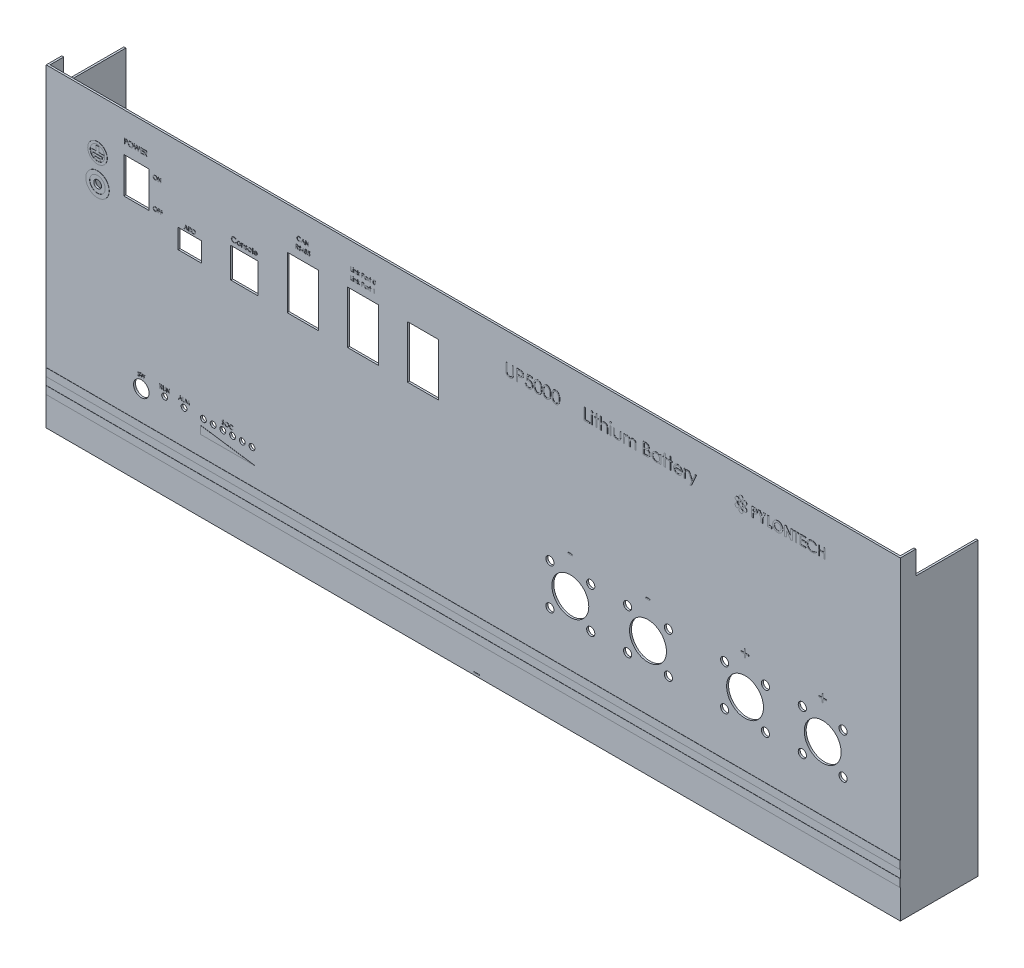
SolidWorks part; units mm, degrees
ref_plane "Front Plane" through (0, 0, 0) normal (0, 0, 1) x (1, 0, 0)
ref_plane "Top Plane" through (0, 0, 0) normal (0, 1, 0) x (1, 0, 0)
ref_plane "Right Plane" through (0, 0, 0) normal (1, 0, 0) x (0, 0, -1)
sketch "Sketch1" plane through (0, 0, 0) normal (0, 1, 0) x (1, 0, 0)
  line L0 (-220, 40) -> (-219, 40)
  line L1 (-220, 0) -> (220, 0)
  line L2 (0, 0) -> (0, 1) construction
  line L3 (-219, 1) -> (219, 1)
  line L6 (220, 0) -> (220, 40)
  line L7 (220, 40) -> (219, 40)
  line L8 (219, 1) -> (219, 40)
  line L9 (-219, 1) -> (-219, 40)
  line L10 (-220, 0) -> (-220, 40)
  dimension "D1" = 1
  dimension "D2" = 40
  dimension "D3" = 1
  dimension "D4" = 440
extrude "Boss-Extrude1" add sketch "Sketch1" along normal blind 162
sketch "Sketch2" plane through (220, 0, 0) normal (1, 0, 0) x (0, 0, -1)
  line L0 (0, 162) -> (0, 0) construction
  line L1 (40, 162) -> (8, 162)
  line L2 (40, 162) -> (40, 150)
  line L3 (40, 150) -> (8, 150)
  line L4 (8, 162) -> (8, 150)
  dimension "D1" = 8
  dimension "D2" = 12
extrude "Cut-Extrude1" cut sketch "Sketch2" against normal through all
sketch "Sketch3" plane through (0, 0, 0) normal (0, 0, 1) x (1, 0, 0)
  line L0 (50, 60) -> (90, 60) construction
  line L1 (-180, 142) -> (-167, 142)
  line L2 (-180, 142) -> (-180, 123.5)
  line L3 (-180, 123.5) -> (-167, 123.5)
  line L4 (-167, 142) -> (-167, 123.5)
  line L5 (-152, 123.5) -> (-140, 123.5)
  line L6 (-152, 123.5) -> (-152, 113.5)
  line L7 (-152, 113.5) -> (-140, 113.5)
  line L8 (-140, 123.5) -> (-140, 113.5)
  line L9 (-125, 129) -> (-110.8, 129)
  line L10 (-125, 129) -> (-125, 113.5)
  line L11 (-125, 113.5) -> (-110.8, 113.5)
  line L12 (-110.8, 129) -> (-110.8, 113.5)
  line L13 (-95.8, 140.5) -> (-79.8, 140.5)
  line L14 (-95.8, 140.5) -> (-95.8, 113.5)
  line L15 (-95.8, 113.5) -> (-79.8, 113.5)
  line L16 (-79.8, 140.5) -> (-79.8, 113.5)
  line L17 (-64.8, 140.5) -> (-48.8, 140.5)
  line L18 (-64.8, 140.5) -> (-64.8, 113.5)
  line L19 (-64.8, 113.5) -> (-48.8, 113.5)
  line L20 (-48.8, 140.5) -> (-48.8, 113.5)
  line L21 (90, 60) -> (70, 60) construction
  line L22 (70, 60) -> (70, 70.5) construction
  line L23 (70, 70.5) -> (60.5, 70.5) construction
  line L24 (140, 60) -> (180, 60) construction
  line L25 (180, 60) -> (160, 60) construction
  line L26 (160, 60) -> (160, 70.5) construction
  line L27 (160, 70.5) -> (150.5, 70.5) construction
  line L28 (-220, 0) -> (220, 0) construction
  line L29 (220, 162) -> (220, 0) construction
  line L30 (-220, 162) -> (220, 162) construction
  line L31 (-220, 162) -> (-220, 0) construction
  line L32 (-193.5, 122) -> (-173.5, 122) construction
  line L33 (-173.5, 122) -> (-173.5, 142) construction
  line L34 (-140, 113.5) -> (-125, 113.5) construction
  line L35 (-110.8, 113.5) -> (-95.8, 113.5) construction
  line L36 (-79.8, 113.5) -> (-64.8, 113.5) construction
  line L37 (-48.8, 113.5) -> (-33.8, 113.5) construction
  line L39 (-33.8, 113.5) -> (-17.8, 113.5)
  line L40 (-33.8, 113.5) -> (-33.8, 140.5)
  line L41 (-33.8, 140.5) -> (-17.8, 140.5)
  line L42 (-17.8, 113.5) -> (-17.8, 140.5)
  circle A0 centre (-193.5, 122) radius 2
  circle A1 centre (50, 60) radius 9.5
  circle A5 centre (60.5, 70.5) radius 2.1
  circle A6 centre (60.5, 49.5) radius 2.1
  circle A7 centre (39.5, 49.5) radius 2.1
  circle A8 centre (39.5, 70.5) radius 2.1
  circle A9 centre (100.5, 70.5) radius 2.1
  circle A10 centre (100.5, 49.5) radius 2.1
  circle A11 centre (90, 60) radius 9.5
  circle A12 centre (79.5, 49.5) radius 2.1
  circle A13 centre (79.5, 70.5) radius 2.1
  circle A14 centre (140, 60) radius 9.5
  circle A15 centre (150.5, 70.5) radius 2.1
  circle A16 centre (150.5, 49.5) radius 2.1
  circle A17 centre (129.5, 49.5) radius 2.1
  circle A18 centre (129.5, 70.5) radius 2.1
  circle A19 centre (190.5, 70.5) radius 2.1
  circle A20 centre (190.5, 49.5) radius 2.1
  circle A21 centre (180, 60) radius 9.5
  circle A22 centre (169.5, 49.5) radius 2.1
  circle A23 centre (169.5, 70.5) radius 2.1
  point P35 (50, 60)
  point P59 (140, 60)
  dimension "D3" = 19
  dimension "D5" = 4.2
  dimension "D14" = 4
  dimension "D2" = 21
  dimension "D6" = 40
  dimension "D7" = 60
  dimension "D8" = 50
  dimension "D9" = 40
  dimension "D10" = 13
  dimension "D11" = 18.5
  dimension "D12" = 20
  dimension "D13" = 40
  dimension "D15" = 20
  dimension "D16" = 20
  dimension "D17" = 12
  dimension "D18" = 10
  dimension "D19" = 15
  dimension "D20" = 15
  dimension "D21" = 15.5
  dimension "D22" = 14.2
  dimension "D23" = 16
  dimension "D24" = 27
  dimension "D4" = 2
  dimension "D1" = 4
extrude "Cut-Extrude2" cut sketch "Sketch3" against normal blind 132
sketch "Sketch4" plane through (0, 0, 0) normal (0, 0, 1) x (1, 0, 0)
  line L0 (-220, 162) -> (-220, 0) construction
  line L1 (-220, 27) -> (220, 27)
  line L2 (-220, 27) -> (-220, 23)
  line L3 (-220, 23) -> (220, 23)
  line L4 (220, 27) -> (220, 23)
  line L5 (220, 162) -> (220, 0) construction
  line L6 (220, 81) -> (-220, 81) construction
  line L7 (-220, 19) -> (220, 19)
  line L8 (-220, 19) -> (-220, 15)
  line L9 (-220, 15) -> (220, 15)
  line L10 (220, 19) -> (220, 15)
  line L11 (0, 27) -> (0, 23) construction
  line L12 (0, 23) -> (0, 19) construction
  line L13 (0, 19) -> (0, 15) construction
  line L14 (0, 21) -> (220, 21) construction
  line L15 (0, 27) -> (0, 142) construction
  line L16 (0, 142) -> (220, 142) construction
  line L17 (-193.5, 122) -> (-193.5, 136) construction
  line L18 (-193.5, 136) -> (-192.75, 136) construction
  line L55 (-194.25, 132.6) -> (-192.75, 132.6) construction
  line L57 (-192.75, 136) -> (-190.25, 136) construction
  line L58 (-196.75, 136.5) -> (-192.75, 136.5) construction
  line L59 (-196.75, 136.5) -> (-196.75, 135.5) construction
  line L61 (-190.25, 136.5) -> (-190.25, 135.5) construction
  line L66 (-195, 132.9) -> (-194.25, 132.9) construction
  line L67 (-195, 132.9) -> (-195, 133.9) construction
  line L69 (-192, 132.9) -> (-192, 133.9) construction
  line L70 (-194.25, 135.2) -> (-195.9628, 135.2) construction
  line L73 (-192.75, 132.9) -> (-192, 132.9) construction
  line L74 (-194.25, 132.6) -> (-194.25, 132.9) construction
  line L75 (-195, 133.9) -> (-194.25, 133.9) construction
  line L80 (-194.25, 135.5) -> (-196.75, 135.5) construction
  line L81 (-196.75, 136.5) -> (-194.25, 136.5) construction
  line L83 (-192.75, 139.1) -> (-192.75, 136.5) construction
  line L84 (-192.75, 136.5) -> (-190.25, 136.5) construction
  line L85 (-190.25, 135.5) -> (-192.75, 135.5) construction
  line L86 (-192.75, 135.5) -> (-192.75, 135.2) construction
  line L87 (-192.75, 135.2) -> (-191.0372, 135.2) construction
  line L90 (-192.75, 133.9) -> (-192, 133.9) construction
  line L91 (-192.75, 132.6) -> (-192.75, 132.9) construction
  line L107 (-194.25, 136.5) -> (-196.75, 136.5) construction
  line L108 (-196.75, 136.5) -> (-196.75, 135.5) construction
  line L115 (-194.25, 133.9) -> (-195, 133.9) construction
  line L116 (-195, 133.9) -> (-195, 132.9) construction
  line L117 (-195, 132.9) -> (-194.25, 132.9) construction
  line L119 (-192.75, 139.1) -> (-192.75, 136.5) construction
  line L120 (-192.75, 136.5) -> (-190.25, 136.5) construction
  line L121 (-190.25, 136.5) -> (-190.25, 135.5) construction
  line L122 (-190.25, 135.5) -> (-192.75, 135.5) construction
  line L123 (-192.75, 135.5) -> (-192.75, 135.2) construction
  line L124 (-192.75, 135.2) -> (-191.0372, 135.2) construction
  line L132 (-192.75, 132.6) -> (-194.25, 132.6) construction
  line L133 (-194.25, 132.6) -> (-194.25, 132.9) construction
  line L135 (-194.25, 135.2) -> (-194.25, 135.5) construction
  line L136 (-194.25, 136.5) -> (-194.25, 139.1) construction
  line L137 (-194.25, 139.1) -> (-192.75, 139.1) construction
  line L138 (-195.9628, 135.2) -> (-195.9628, 134.2) construction
  line L139 (-195.9628, 134.2) -> (-194.25, 134.2) construction
  line L140 (-194.25, 134.2) -> (-194.25, 133.9) construction
  line L141 (-192.75, 133.9) -> (-192.75, 134.2) construction
  line L142 (-192.75, 134.2) -> (-191.0372, 134.2) construction
  line L143 (-191.0372, 134.2) -> (-191.0372, 135.2) construction
  line L144 (-192.75, 136) -> (-192.75, 136.5) construction
  line L145 (-220, 162) -> (220, 162) construction
  circle A0 centre (-193.5, 122) radius 6
  circle A1 centre (-193.5, 122) radius 4
  circle A2 centre (-193.5, 122) radius 2 construction
  circle A3 centre (-193.5, 136) radius 5
  circle A8 centre (-193.5, 136) radius 3.75
  text T0 "       UP5000     Lithium Battery" font "Century Gothic" height 6
  point P36 (-193.5, 132.6)
  point P61 (-193.5, 139.1)
  dimension "D4" = 2
  dimension "D5" = 2
  dimension "D6" = 10
  dimension "D7" = 20
  dimension "D10" = 7.5
  dimension "D9" = 6.5
  dimension "D1" = 4
  dimension "D2" = 60
  dimension "D3" = 4
  dimension "D8" = 14
  dimension "D11" = 1
  dimension "D12" = 6.5
  dimension "D13" = 4.9255
  dimension "D14" = 3
  dimension "D15" = 0.3
  dimension "D16" = 1.5
extrude "Boss-Extrude2" add sketch "Sketch4" along normal blind 0.1
sketch "Sketch5" plane through (0, 0, 0) normal (0, 0, 1) x (1, 0, 0)
  line L0 (-192.75, 139.1) -> (-194.25, 139.1)
  line L1 (-194.25, 139.1) -> (-194.25, 136.5)
  line L2 (-194.25, 136.5) -> (-196.75, 136.5)
  line L3 (-196.75, 136.5) -> (-196.75, 135.5)
  line L7 (-195.9628, 135.2) -> (-195.9628, 134.2)
  line L11 (-195, 133.9) -> (-195, 132.9)
  line L12 (-195, 132.9) -> (-194.25, 132.9)
  line L13 (-194.25, 132.9) -> (-194.25, 132.6)
  line L14 (-194.25, 132.6) -> (-192.75, 132.6)
  line L15 (-192.75, 132.6) -> (-192.75, 132.9)
  line L16 (-192.75, 132.9) -> (-192, 132.9)
  line L17 (-192, 132.9) -> (-192, 133.9)
  line L21 (-191.0372, 134.2) -> (-191.0372, 135.2)
  line L25 (-190.25, 135.5) -> (-190.25, 136.5)
  line L26 (-190.25, 136.5) -> (-192.75, 136.5)
  line L27 (-192.75, 136.5) -> (-192.75, 139.1)
  line L29 (-196.75, 135.5) -> (-190.25, 135.5)
  line L30 (-195.9628, 135.2) -> (-191.0372, 135.2)
  line L32 (-191.0372, 134.2) -> (-195.9628, 134.2)
  line L33 (-195, 133.9) -> (-192, 133.9)
extrude "Boss-Extrude3" add sketch "Sketch5" along normal blind 0.1
sketch "Sketch6" plane through (0, 0, 0) normal (0, 0, 1) x (1, 0, 0)
  line L0 (-180, 142) -> (-180, 147) construction
  line L1 (-180, 147) -> (-167, 147) construction
  line L2 (-167, 147) -> (-167, 142) construction
  line L3 (-167, 132.75) -> (-165.0088, 132.75) construction
  line L4 (-167, 123.5) -> (-167, 142) construction
  line L5 (-165.0088, 132.75) -> (-165.0088, 138.75) construction
  line L6 (-165.0088, 138.75) -> (-160.0088, 138.75) construction
  line L7 (-165.0088, 124.75) -> (-131.6322, 124.75) construction
  line L8 (-165.0088, 124.75) -> (-165.0088, 132.75) construction
  line L9 (-152, 123.5) -> (-152, 124.5) construction
  line L10 (-152, 124.5) -> (-140, 124.5) construction
  line L11 (-140, 124.5) -> (-140, 123.5) construction
  line L12 (-125, 129) -> (-125, 131) construction
  line L13 (-125, 131) -> (-110.8, 131) construction
  line L14 (-110.8, 131) -> (-110.8, 129) construction
  line L15 (-95.8, 140.5) -> (-95.8, 148.5) construction
  line L16 (-95.8, 148.5) -> (-79.8, 148.5) construction
  line L17 (-79.8, 148.5) -> (-79.8, 140.5) construction
  line L18 (-79.8, 140.5) -> (-95.8, 140.5) construction
  line L19 (-95.8, 113.5) -> (-95.8, 144.5) construction
  line L20 (-95.8, 144.5) -> (-79.8, 144.5) construction
  line L21 (-79.8, 144.5) -> (-79.8, 113.5) construction
  line L22 (-95.8, 140.5) -> (-95.8, 113.5) construction
  line L25 (-64.8, 140.5) -> (-64.8, 148.5) construction
  line L26 (-64.8, 148.5) -> (-48.8, 148.5) construction
  line L27 (-48.8, 148.5) -> (-48.8, 140.5) construction
  line L28 (-64.8, 140.5) -> (-64.8, 113.5) construction
  line L29 (-64.8, 113.5) -> (-64.8, 144.5) construction
  line L30 (-64.8, 144.5) -> (-48.8, 144.5) construction
  line L31 (-48.8, 144.5) -> (-48.8, 113.5) construction
  line L32 (-48.8, 140.5) -> (-64.8, 140.5) construction
  line L34 (39.5, 70.5) -> (39.5, 76.5) construction
  line L36 (60.5, 70.5) -> (60.5, 76.5) construction
  line L37 (60.5, 76.5) -> (39.5, 76.5) construction
  line L39 (79.5, 70.5) -> (79.5, 76.5) construction
  line L40 (129.5, 76.5) -> (150.5, 76.5) construction
  line L41 (100.5, 70.5) -> (100.5, 76.5) construction
  line L42 (100.5, 76.5) -> (79.5, 76.5) construction
  line L44 (129.5, 70.5) -> (129.5, 76.5) construction
  line L46 (150.5, 70.5) -> (150.5, 76.5) construction
  line L48 (169.5, 70.5) -> (169.5, 76.5) construction
  line L50 (190.5, 70.5) -> (190.5, 76.5) construction
  line L51 (190.5, 76.5) -> (169.5, 76.5) construction
  text T0 "POWER" font "Century Gothic" height 2.5
  text T1 "ON" font "Century Gothic" height 2
  text T2 "OFF" font "Century Gothic" height 2
  text T3 "ADD" font "Century Gothic" height 2
  text T4 "Console" font "Century Gothic" height 2.5
  text T5 "--"
  text T6 "-" font "Century Gothic" height 6
  text T7 "-\r\n" font "Century Gothic" height 6
  text T8 "+" font "Century Gothic" height 6
  text T9 "+" font "Century Gothic" height 6
  text T10 "CAN" font "Century Gothic" height 2
  text T11 "RS485" font "Century Gothic" height 2
  text T12 "Link Port 0" font "Century Gothic" height 2
  text T13 "Link Port 1" font "Century Gothic" height 2
  dimension "D1" = 5
  dimension "D2" = 5
  dimension "D3" = 6
  dimension "D4" = 8
  dimension "D5" = 1
  dimension "D6" = 2
  dimension "D7" = 6
  dimension "D8" = 8
extrude "Boss-Extrude4" add sketch "Sketch6" along normal blind 0.1
sketch "Sketch7" plane through (0, 0, 0) normal (0, 0, 1) x (1, 0, 0)
  line L0 (80.1892, 162) -> (80.1892, 142) construction
  line L1 (-220, 162) -> (220, 162) construction
  line L2 (80.1892, 142) -> (165, 142) construction
  line L4 (165, 142) -> (220, 142) construction
  line L5 (220, 162) -> (220, 27) construction
  text T0 "<b>PYLON</b>" font "Century Gothic" height 5
  text T1 "TECH" font "Century Gothic" height 5
  dimension "D1" = 55
  dimension "D2" = 20
extrude "Boss-Extrude5" add sketch "Sketch7" along normal blind 0.1
sketch "Sketch8" plane through (0, 0, 0) normal (0, 0, 1) x (1, 0, 0)
  line L0 (138, 162) -> (138, 148) construction
  line L1 (-220, 162) -> (220, 162) construction
  line L2 (138, 148) -> (138, 145) construction
  line L3 (138, 145) -> (138, 142) construction
  line L4 (138, 145) -> (140, 145) construction
  line L6 (138, 146.5) -> (140, 146.5) construction
  line L7 (140, 146.5) -> (140, 143.5) construction
  line L8 (137.75, 142.9682) -> (137.75, 144.0318)
  line L9 (139.75, 145.5318) -> (140.25, 145.5318) construction
  line L10 (139.75, 145.5318) -> (139.75, 144.4682)
  line L11 (139.75, 144.4682) -> (140.25, 144.4682) construction
  line L12 (140.25, 145.5318) -> (140.25, 144.4682)
  line L13 (137.75, 147.0318) -> (138.25, 147.0318) construction
  line L14 (137.75, 147.0318) -> (137.75, 145.9682)
  line L15 (137.75, 145.9682) -> (138.25, 145.9682) construction
  line L16 (138.25, 147.0318) -> (138.25, 145.9682)
  line L17 (138.25, 142.9682) -> (138.25, 144.0318)
  line L18 (136.25, 145.5318) -> (136.25, 144.4682)
  line L19 (135.75, 145.5318) -> (135.75, 144.4682)
  line L20 (220, 162) -> (220, 27) construction
  arc A0 (140.25, 145.5318) -> (139.75, 145.5318) centre (140, 146.5) ccw
  arc A1 (139.75, 144.4682) -> (140.25, 144.4682) centre (140, 143.5) ccw
  arc A2 (137.75, 145.9682) -> (137.75, 144.0318) centre (138, 145) ccw
  arc A3 (138.25, 147.0318) -> (137.75, 147.0318) centre (138, 148) ccw
  arc A4 (137.75, 142.9682) -> (138.25, 142.9682) centre (138, 142) ccw
  arc A5 (138.25, 144.0318) -> (138.25, 145.9682) centre (138, 145) ccw
  arc A6 (135.75, 145.5318) -> (136.25, 145.5318) centre (136, 146.5) cw
  arc A7 (136.25, 144.4682) -> (135.75, 144.4682) centre (136, 143.5) cw
  point P19 (140, 145.5318)
  point P22 (138, 147.0318)
  dimension "D1" = 2
  dimension "D3" = 3
  dimension "D2" = 2
  dimension "D4" = 0.5
  dimension "D5" = 14
  dimension "D6" = 82
extrude "Boss-Extrude6" add sketch "Sketch8" along normal blind 0.1
sketch "Sketch9" plane through (0, 0, 0) normal (0, 0, 1) x (1, 0, 0)
  line L0 (-167, 123.5) -> (-167, 27) construction
  line L1 (220, 27) -> (-220, 27) construction
  line L2 (-220, 46) -> (220, 46) construction
  line L3 (-220, 162) -> (-220, 27) construction
  line L4 (220, 162) -> (220, 27) construction
  line L5 (-159, 44.5) -> (-149, 44.5) construction
  line L6 (-149, 44.5) -> (-139, 44.5) construction
  line L7 (-139, 44.5) -> (-114, 44.5) construction
  circle A0 centre (-171, 42) radius 4
  circle A1 centre (-159, 44.5) radius 1.5
  circle A2 centre (-149, 44.5) radius 1.5
  circle A3 centre (-139, 44.5) radius 1.5
  circle A4 centre (-134, 44.5) radius 1.5
  circle A5 centre (-129, 44.5) radius 1.5
  circle A6 centre (-124, 44.5) radius 1.5
  circle A7 centre (-119, 44.5) radius 1.5
  circle A8 centre (-114, 44.5) radius 1.5
  dimension "D1" = 8
  dimension "D2" = 3
  dimension "D3" = 15
  dimension "D4" = 10
  dimension "D5" = 8
  dimension "D6" = 10
  dimension "D8" = 25
  dimension "D7" = 6
extrude "Cut-Extrude3" cut sketch "Sketch9" against normal blind 3
sketch "Sketch10" plane through (0, 0, 0) normal (0, 0, 1) x (1, 0, 0)
  line L0 (-140.5, 41) -> (-140.5, 37)
  line L1 (-140.5, 37) -> (-112.5, 37)
  line L2 (-112.5, 37) -> (-140.5, 41)
  line L3 (-140.5, 47) -> (-112.5, 47) construction
  line L4 (220, 27) -> (-220, 27) construction
  line L5 (-140.5, 41) -> (-140.5, 47) construction
  line L6 (-162, 47) -> (-156, 47) construction
  line L7 (-149, 44.5) -> (-149, 47) construction
  line L8 (-112.5, 47) -> (-112.5, 37) construction
  line L9 (-152, 47) -> (-146, 47) construction
  line L10 (-171, 42) -> (-171, 47) construction
  line L11 (-159, 44.5) -> (-159, 47) construction
  line L12 (-174, 47) -> (-168, 47) construction
  circle A1 centre (-139, 44.5) radius 1.5 construction
  circle A2 centre (-114, 44.5) radius 1.5 construction
  text T0 "RUN" font "Century Gothic" height 2
  text T1 "ALM" font "Century Gothic" height 2
  text T2 "SOC" font "Century Gothic" height 2
  text T3 "SW" font "Century Gothic" height 2
  point P29 (-171, 47)
  dimension "D1" = 4
  dimension "D2" = 10
  dimension "D3" = 6
  dimension "D4" = 6
extrude "Boss-Extrude7" add sketch "Sketch10" along normal blind 0.1
